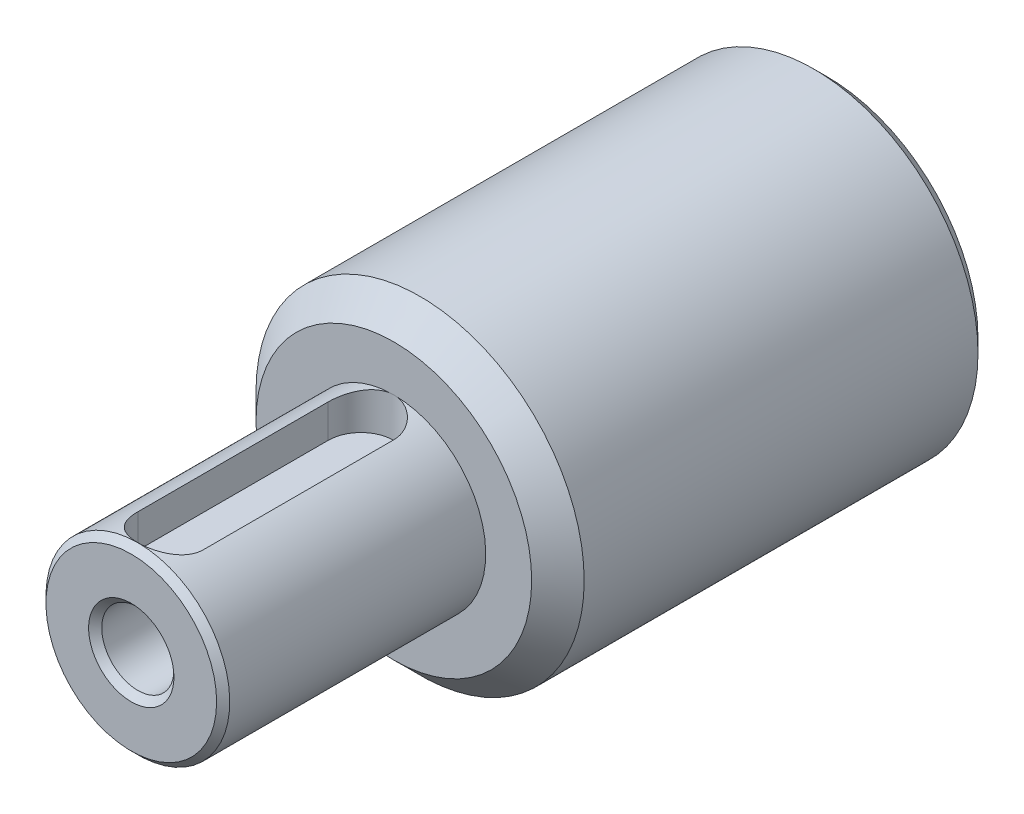
SolidWorks part; units mm, degrees
material "普通碳钢"
ref_plane "前视基准面" through (0, 0, 0) normal (0, 0, 1) x (1, 0, 0)
ref_plane "上视基准面" through (0, 0, 0) normal (0, 1, 0) x (1, 0, 0)
ref_plane "右视基准面" through (0, 0, 0) normal (1, 0, 0) x (0, 0, -1)
sketch "草图1" plane through (0, 0, 0) normal (0, 0, 1) x (1, 0, 0)
  circle A0 centre (0, 0) radius 12.5
  dimension "D1" = 25
extrude "拉伸1" add sketch "草图1" along normal blind 33
sketch "草图4" plane through (0, 0, 33) normal (0, 0, 1) x (1, 0, 0)
  circle A0 centre (0, 0) radius 7
  dimension "D1" = 14
extrude "拉伸2" add sketch "草图4" against normal blind 3
sketch "草图7" plane through (0, 0, 33) normal (0, 0, 1) x (1, 0, 0)
  circle A0 centre (0, 0) radius 7
extrude "拉伸3" add sketch "草图7" along normal blind 20
chamfer "倒角1" distance 2 angle 45 1 edges at (12.5, 0, 33)
ref_plane "基准面1" through (0, 7, 0) normal (0, 1, 0) x (-1, 0, 0)
sketch "草图8" plane through (0, 7, 0) normal (0, 1, 0) x (-1, 0, 0)
  line L0 (7, 53) -> (-7, 53) construction
  line L1 (7, 33) -> (-7, 33) construction
  line L2 (-2.5, 50) -> (-2.5, 35.5)
  line L3 (2.5, 50) -> (2.5, 35.5)
  arc A0 (2.5, 50) -> (-2.5, 50) centre (0, 50) ccw
  arc A1 (-2.5, 35.5) -> (2.5, 35.5) centre (0, 35.5) ccw
  dimension "D1" = 5
  dimension "D2" = 5
  dimension "D3" = 3
  dimension "D4" = 2.5
extrude "切除-拉伸4" cut sketch "草图8" against normal blind 3
chamfer "倒角2" distance 0.5 angle 45 1 edges at (7, 0, 53)
chamfer "倒角3" distance 1 angle 45 1 edges at (12.5, 0, 0)
sketch "草图9" plane through (0, 0, 0) normal (0, 0, -1) x (-1, 0, 0)
  circle A0 centre (0, 0) radius 7
extrude "切除-拉伸5" cut sketch "草图9" against normal blind 28
sketch "草图10" plane through (0, 0, 0) normal (0, 0, -1) x (-1, 0, 0)
  line L1 (-2.5, 9) -> (2.5, 9)
  line L2 (-2.5, 9) -> (-2.5, 4.3323)
  line L3 (-2.5, 4.3323) -> (2.5, 4.3323)
  line L4 (2.5, 9) -> (2.5, 4.3323)
extrude "切除-拉伸6" cut sketch "草图10" against normal blind 26
chamfer "倒角4" distance 0.5 angle 45 1 edges at (0, -7, 0)
sketch "草图11" plane through (0, 0, 53) normal (0, 0, 1) x (1, 0, 0)
  circle A0 centre (0, 0) radius 2.75
  dimension "D1" = 5.5
extrude "切除-拉伸7" cut sketch "草图11" against normal blind 50
chamfer "倒角5" distance 0.5 angle 45 1 edges at (2.75, 0, 53)
fillet "圆角1" radius 1 1 edges at (-7, 0, 28)
